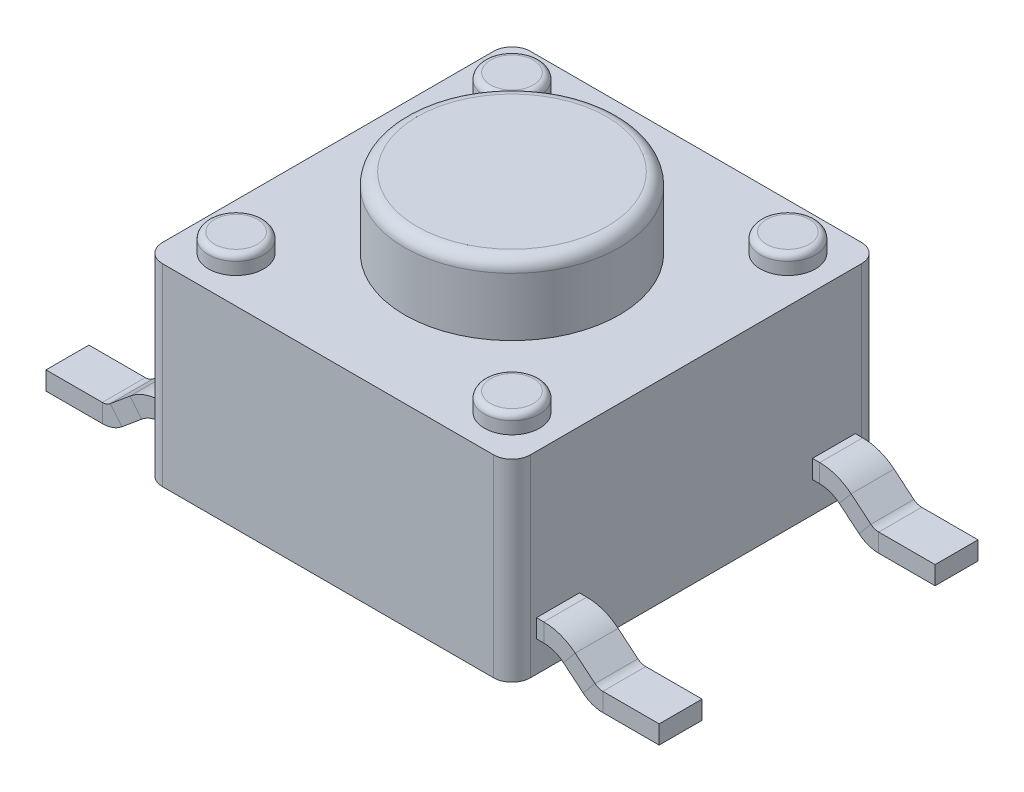
SolidWorks part; units mm, degrees
ref_plane "Front" through (0, 0, 0) normal (0, 0, 1) x (1, 0, 0)
ref_plane "Top" through (0, 0, 0) normal (0, 1, 0) x (1, 0, 0)
ref_plane "Right" through (0, 0, 0) normal (1, 0, 0) x (0, 0, -1)
sketch "Sketch1" plane through (0, 0, 0) normal (0, 1, 0) x (1, 0, 0)
  line L1 (-2.7, 3) -> (2.7, 3)
  line L2 (-3, 2.7) -> (-3, -2.7)
  line L3 (-2.7, -3) -> (2.7, -3)
  line L4 (3, 2.7) -> (3, -2.7)
  line L5 (-3, 3) -> (3, -3) construction
  line L6 (-3, -3) -> (3, 3) construction
  arc A0 (-3, -2.7) -> (-2.7, -3) centre (-2.7, -2.7) ccw
  arc A1 (-2.7, 3) -> (-3, 2.7) centre (-2.7, 2.7) ccw
  arc A2 (2.7, 3) -> (3, 2.7) centre (2.7, 2.7) cw
  arc A3 (2.7, -3) -> (3, -2.7) centre (2.7, -2.7) ccw
  point P0 (0, 0)
  dimension "D3" = 0.3
  dimension "D1" = 6
  dimension "D2" = 6
extrude "Boss-Extrude1" add sketch "Sketch1" along normal blind 3.15
sketch "Sketch2" plane through (0, 3.15, 0) normal (0, 1, 0) x (1, 0, 0)
  circle A0 centre (0, 0) radius 1.75
  dimension "D1" = 3.5
extrude "Boss-Extrude2" add sketch "Sketch2" along normal blind 1.15
fillet "Fillet1" radius 0.2 1 edges at (0, 4.3, 1.75)
sketch "Sketch3" plane through (0, 3.15, 0) normal (0, 1, 0) x (1, 0, 0)
  line L1 (-2.25, -2.25) -> (2.25, -2.25) construction
  line L2 (-2.25, -2.25) -> (-2.25, 2.25) construction
  line L3 (-2.25, 2.25) -> (2.25, 2.25) construction
  line L4 (2.25, -2.25) -> (2.25, 2.25) construction
  line L5 (-2.25, -2.25) -> (2.25, 2.25) construction
  line L6 (-2.25, 2.25) -> (2.25, -2.25) construction
  circle A0 centre (-2.25, 2.25) radius 0.45
  circle A1 centre (2.25, 2.25) radius 0.45
  circle A2 centre (2.25, -2.25) radius 0.45
  circle A3 centre (-2.25, -2.25) radius 0.45
  point P0 (0, 0)
  dimension "D2" = 0.9
  dimension "D1" = 4.5
extrude "Boss-Extrude3" add sketch "Sketch3" along normal blind 0.3
sketch "Sketch4" plane through (3, 0, 0) normal (1, 0, 0) x (0, 0, -1)
  line L1 (-2.6, 0.8) -> (-1.9, 0.8)
  line L2 (-2.6, 0.8) -> (-2.6, 0.5)
  line L3 (-2.6, 0.5) -> (-1.9, 0.5)
  line L4 (-1.9, 0.8) -> (-1.9, 0.5)
  line L5 (0, 0) -> (0, 2.0954) construction
  line L6 (-2.7, 0) -> (2.7, 0) construction
  dimension "D1" = 0.7
  dimension "D2" = 0.3
  dimension "D3" = 0.5
  dimension "D4" = 5.2
ref_plane "Plane1" through (0, 0, 2.6) normal (0, 0, 1) x (1, 0, 0)
sketch "Sketch5" plane through (0, 0, 2.6) normal (0, 0, 1) x (1, 0, 0)
  line L0 (3, 0.5) -> (3.119, 0.5)
  line L1 (3.4391, 0.3841) -> (3.7609, 0.1159)
  line L2 (4.081, 0) -> (4.2, 0) construction
  line L3 (4.081, 0) -> (5, 0)
  arc A0 (3.7609, 0.1159) -> (4.081, 0) centre (4.081, 0.5) ccw
  arc A1 (3.119, 0.5) -> (3.4391, 0.3841) centre (3.119, 0) cw
  point P8 (3.9, 0)
  point P11 (3.3, 0.5)
  dimension "D5" = 0.5
  dimension "D1" = 5
  dimension "D2" = 1.2
  dimension "D3" = 0.3
  dimension "D4" = 0.3
sweep "Sweep1" add profiles "Sketch4" path "Sketch5"
mirror "Mirror1" about plane through (0, 0, 0) normal (0, 0, 1) of "Sweep1"
mirror "Mirror2" about plane through (0, 0, 0) normal (1, 0, 0) of "Mirror1"
fillet "Fillet2" radius 0.1 4 edges at (-2.25, 3.45, -1.8) (2.25, 3.45, -1.8) (2.25, 3.45, 2.7) (-2.25, 3.45, 2.7)
